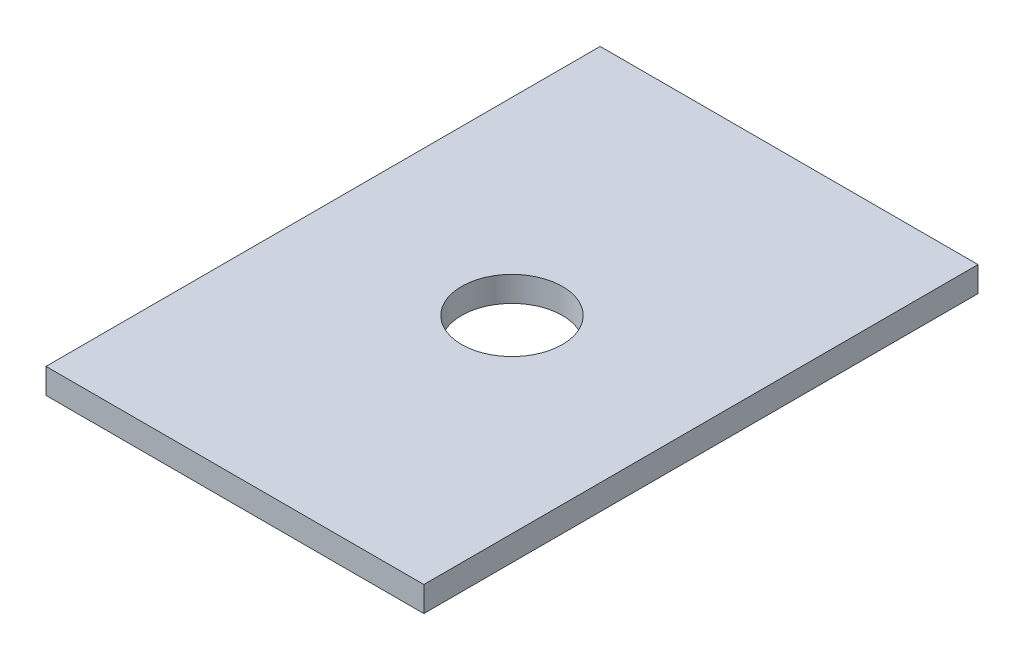
SolidWorks part; units mm, degrees
ref_plane "Front Plane" through (0, 0, 0) normal (0, 0, 1) x (1, 0, 0)
ref_plane "Top Plane" through (0, 0, 0) normal (0, 1, 0) x (1, 0, 0)
ref_plane "Right Plane" through (0, 0, 0) normal (1, 0, 0) x (0, 0, -1)
sketch "Sketch2" plane through (0, 0, 0) normal (0, 1, 0) x (1, 0, 0)
  line L1 (-75, -110) -> (75, -110)
  line L2 (-75, -110) -> (-75, 110)
  line L3 (-75, 110) -> (75, 110)
  line L4 (75, -110) -> (75, 110)
  line L5 (-75, -110) -> (75, 110) construction
  line L6 (-75, 110) -> (75, -110) construction
  circle A0 centre (0, 0) radius 20
  point P0 (0, 0)
  dimension "D2" = 40
  dimension "D1" = 220
extrude "Boss-Extrude3" add sketch "Sketch2" along normal blind 10
sketch "Sketch4" plane through (0, 10, 0) normal (0, 1, 0) x (1, 0, 0)
  line L7 (22.2049, 38.5873) -> (42.2049, 18.5873) construction
  line L8 (42.2049, 38.5873) -> (22.2049, 18.5873) construction
  line L9 (42.2049, 18.5873) -> (22.2049, 18.5873)
  line L10 (22.2049, 38.5873) -> (22.2049, 18.5873)
  line L11 (42.2049, 38.5873) -> (22.2049, 38.5873)
  line L12 (42.2049, 38.5873) -> (42.2049, 18.5873)
  line L15 (38.5873, -22.2049) -> (18.5873, -42.2049) construction
  line L16 (38.5873, -42.2049) -> (18.5873, -22.2049) construction
  line L17 (18.5873, -42.2049) -> (18.5873, -22.2049)
  line L18 (38.5873, -22.2049) -> (18.5873, -22.2049)
  line L19 (38.5873, -42.2049) -> (38.5873, -22.2049)
  line L20 (38.5873, -42.2049) -> (18.5873, -42.2049)
  point P13 (32.2049, 28.5873)
  point P20 (28.5873, -32.2049)
extrude "Cut-Extrude1" [suppressed] cut sketch "Sketch4" against normal blind 10
ref_point "Point1"
ref_axis "Axis1" through (0, 10, 0) along (0, -1, 0)
